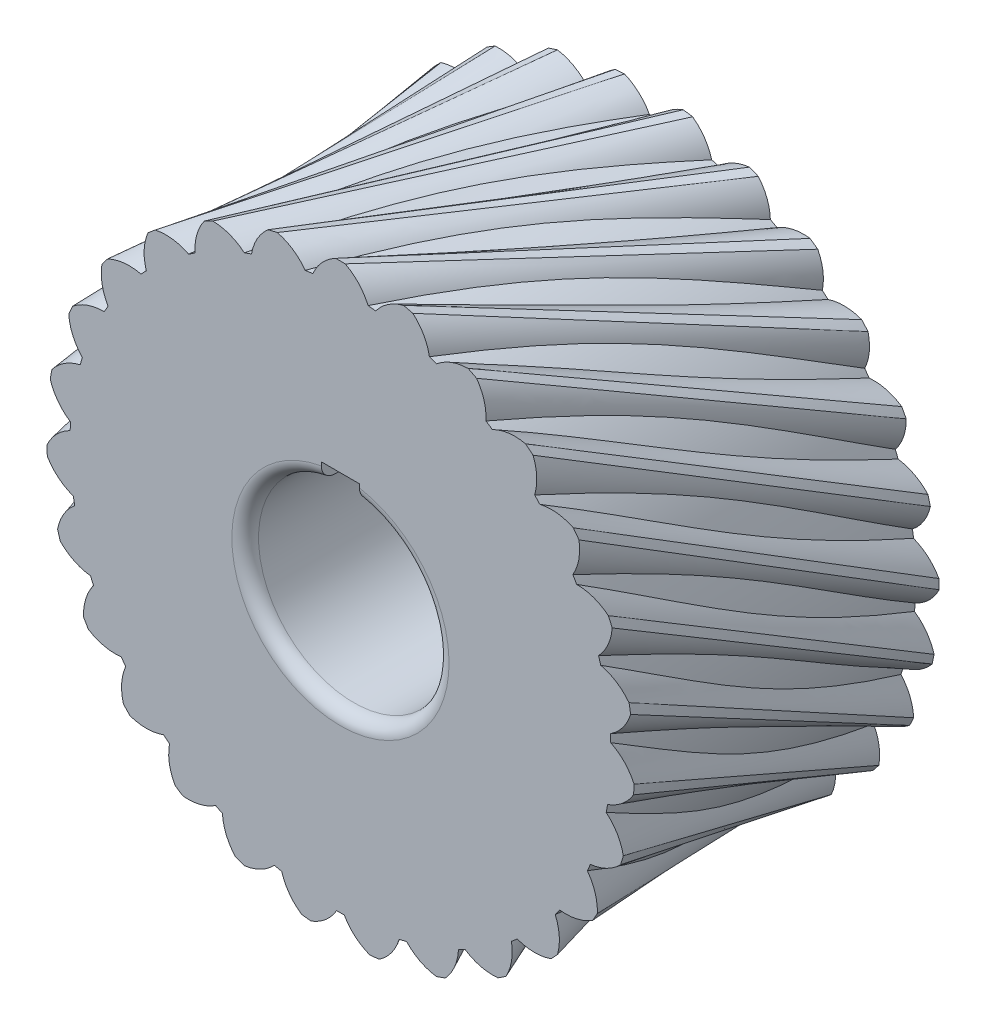
SolidWorks part; units mm, degrees
ref_plane "Plan de face" through (0, 0, 0) normal (0, 0, 1) x (1, 0, 0)
ref_plane "Plan de dessus" through (0, 0, 0) normal (0, 1, 0) x (1, 0, 0)
ref_plane "Plan de droite" through (0, 0, 0) normal (1, 0, 0) x (0, 0, -1)
sketch "Esquisse5" plane through (0, 0, 0) normal (0, 0, 1) x (1, 0, 0)
  circle A0 centre (0, 0) radius 14.2
  circle A1 centre (0, 0) radius 5
  dimension "D1" = 28.4
  dimension "D2" = 10
extrude "Extrusion1" add sketch "Esquisse5" against normal blind 16
sketch "Esquisse1" plane through (0, 0, 0) normal (0, 0, 1) x (1, 0, 0)
  line L0 (0, 8.3971) -> (0, -8.0185) construction
  line L1 (-0.25, 15.4226) -> (0, 0) construction
  line L2 (0, 0) -> (0.25, 15.4226) construction
  line L3 (1.45, 14.1258) -> (0, 0) construction
  line L4 (0, 0) -> (-1.45, 14.1258) construction
  circle A0 centre (0, 0) radius 14.2 construction
  circle A1 centre (0, 0) radius 15.4246 construction
  arc A2 (-0.25, 15.4226) -> (0.25, 15.4226) centre (0, 0) cw
  arc A3 (-1.45, 14.1258) -> (1.45, 14.1258) centre (0, 0) cw
  arc A4 (-1.45, 14.1258) -> (-0.25, 15.4226) centre (0.9578, 13.1014) cw
  arc A5 (1.45, 14.1258) -> (0.25, 15.4226) centre (-0.9578, 13.1014) ccw
  circle A6 centre (0, 0) radius 14.2 construction
  dimension "D1" = 0.5
  dimension "D2" = 2.9
  dimension "D4" = 1.2246
  dimension "D5" = 2.6166
sketch "Esquisse6" plane through (0, 0, -16) normal (0, 0, -1) x (-1, 0, 0)
  line L0 (0, 0) -> (-3.9966, 5.7077) construction
  line L2 (0, 0) -> (-9.0508, 12.4901) construction
  line L3 (0, 0) -> (-8.6413, 12.7768) construction
  line L4 (0, 0) -> (-9.29, 10.7395) construction
  line L5 (0, 0) -> (-6.9144, 12.4028) construction
  line L6 (0, 0) -> (0, 17.9606) construction
  arc A0 (-8.6413, 12.7768) -> (-9.0508, 12.4901) centre (0, 0) ccw
  arc A1 (0.25, 15.4226) -> (-0.25, 15.4226) centre (0, 0) ccw construction
  circle A2 centre (0, 0) radius 15.4246 construction
  arc A3 (-9.29, 10.7395) -> (-9.0508, 12.4901) centre (-6.7301, 11.2814) cw
  arc A4 (-0.25, 15.4226) -> (-1.45, 14.1258) centre (0.9578, 13.1014) ccw construction
  arc A5 (-6.9144, 12.4028) -> (-8.6413, 12.7768) centre (-8.2992, 10.1827) ccw
  arc A6 (-6.9144, 12.4028) -> (-9.29, 10.7395) centre (0, 0) ccw
  circle A7 centre (0, 0) radius 14.2 construction
  dimension "D2" = 0.5
  dimension "D1" = 35
  dimension "D3" = 2.9
loft "Lissage3" add profiles "Esquisse1", "Esquisse6" connector at (1.45, 14.1258, 0) connector at (9.29, 10.7395, -16)
pattern_circular "Répétition circulaire2" count 27 over 360 about axis through (0, 0, -16) along (0, 0, 1) of "Lissage3" reverse direction yes
sketch "Esquisse7" plane through (0, 0, 0) normal (0, 0, 1) x (1, 0, 0)
  line L0 (0, 0) -> (0, 11.0609) construction
  line L1 (-1, 5.8) -> (1, 5.8)
  line L2 (-1, 5.8) -> (-1, 3.5561)
  line L3 (-1, 3.5561) -> (1, 3.5561)
  line L4 (1, 5.8) -> (1, 3.5561)
  dimension "D1" = 2
  dimension "D2" = 5.8
extrude "Enlèv. mat.-Extru.1" cut sketch "Esquisse7" against normal through all
fillet "Congé1" radius 0.7 1 edges at (0, -5, 0)
chamfer "Chanfrein1" distance 0.5 angle 45 1 edges at (0, -5, -16)
